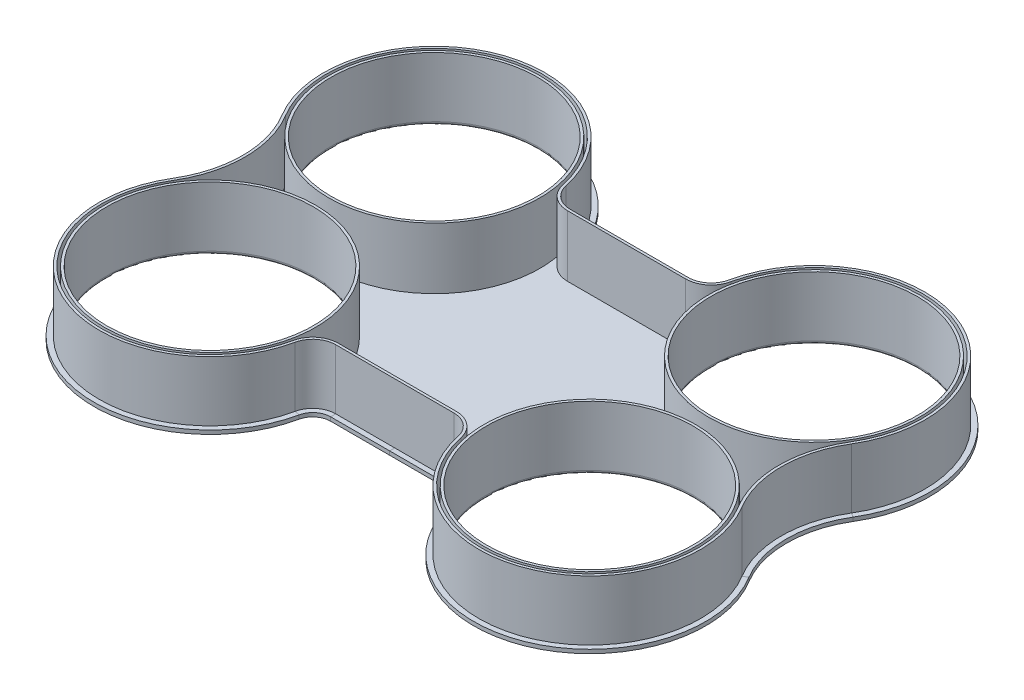
SolidWorks part; units mm, degrees
ref_plane "Front Plane" through (0, 0, 0) normal (0, 0, 1) x (1, 0, 0)
ref_plane "Top Plane" through (0, 0, 0) normal (0, 1, 0) x (1, 0, 0)
ref_plane "Right Plane" through (0, 0, 0) normal (1, 0, 0) x (0, 0, -1)
sketch "Sketch1" plane through (0, 0, 0) normal (0, 1, 0) x (1, 0, 0)
  line L0 (-1720.3603, 0) -> (84297.6564, 0) construction
  line L1 (0, -1720.3603) -> (0, 84297.6564) construction
  line L2 (-23.1653, 46) -> (23.1653, 46)
  line L3 (-23.1653, -46) -> (23.1653, -46)
  arc A0 (111.7183, 21.4824) -> (31.9655, 53.1143) centre (74.5, 44) ccw
  circle A1 centre (74.5, 44) radius 40.5
  arc A2 (111.7183, 21.4824) -> (111.7183, -21.4824) centre (147.2255, 0) ccw
  arc A3 (23.1653, 46) -> (31.9655, 53.1143) centre (23.1653, 55) ccw
  arc A4 (23.1653, -46) -> (31.9655, -53.1143) centre (23.1653, -55) cw
  circle A5 centre (74.5, -44) radius 40.5
  arc A6 (111.7183, -21.4824) -> (31.9655, -53.1143) centre (74.5, -44) cw
  arc A7 (-111.7183, -21.4824) -> (-31.9655, -53.1143) centre (-74.5, -44) ccw
  circle A8 centre (-74.5, -44) radius 40.5
  arc A9 (-23.1653, -46) -> (-31.9655, -53.1143) centre (-23.1653, -55) ccw
  arc A10 (-23.1653, 46) -> (-31.9655, 53.1143) centre (-23.1653, 55) cw
  arc A11 (-111.7183, 21.4824) -> (-111.7183, -21.4824) centre (-147.2255, 0) cw
  circle A12 centre (-74.5, 44) radius 40.5
  arc A13 (-111.7183, 21.4824) -> (-31.9655, 53.1143) centre (-74.5, 44) cw
  point P19 (0, 46)
  point P33 (0, -46)
  dimension "43.5*2" = 87
  dimension "D2" = 3
  dimension "D3" = 83
  dimension "D4" = 9
  dimension "D6" = 175
  dimension "D7" = 236
  dimension "D5" = 46
extrude "Boss-Extrude1" add sketch "Sketch1" along normal blind 25
shell "Shell1" thickness 1 removed face at (0, 25, 0)
fillet "Fillet1" radius 1.5 4 edges at (74.5, 0, -3.5) (74.5, 0, 3.5) (-74.5, 0, 84.5) (-74.5, 0, -84.5)
sketch "Sketch2" plane through (0, 0, 0) normal (1, 0, 0) x (0, 0, -1)
  line L1 (-46, 0) -> (-48, 0)
  line L2 (-46, 0) -> (-46, 1.5)
  line L3 (-46, 1.5) -> (-48, 1.5)
  line L4 (-48, 0) -> (-48, 1.5)
  point P4 (0, 0)
  dimension "D1" = 46
  dimension "D2" = 1.5
  dimension "D3" = 2
sweep "Sweep1" add profiles "Sketch2" path "Sketch1<2>"
sketch "Sketch1<2>" plane through (0, 0, 0) normal (0, 1, 0) x (1, 0, 0) same geometry as "Sketch1"
